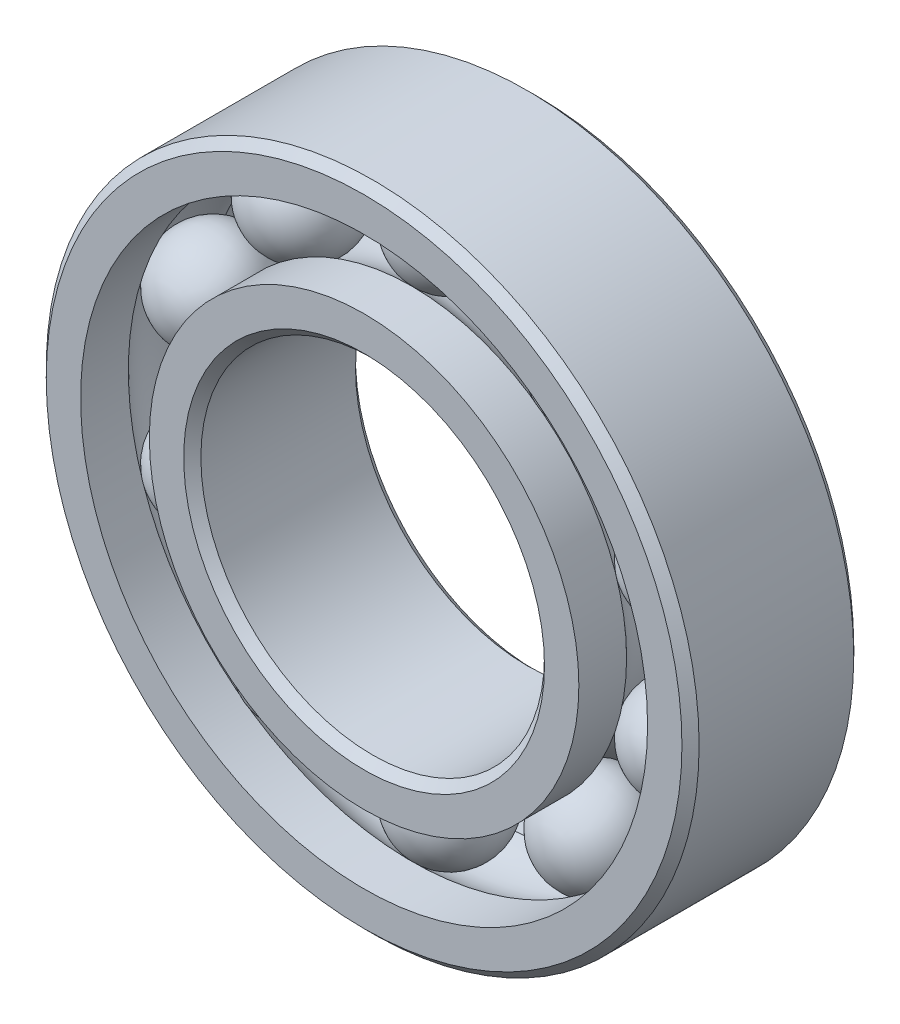
SolidWorks part; units mm, degrees
ref_plane "Front Plane" through (0, 0, 0) normal (0, 0, 1) x (1, 0, 0)
ref_plane "Top Plane" through (0, 0, 0) normal (0, 1, 0) x (1, 0, 0)
ref_plane "Right Plane" through (0, 0, 0) normal (1, 0, 0) x (0, 0, -1)
sketch "Sketch1" plane through (0, 0, 0) normal (0, 0, 1) x (1, 0, 0)
  circle A0 centre (0, 0) radius 9.5
  circle A1 centre (0, 0) radius 5
  dimension "OD" = 19
  dimension "ID" = 10
  dimension "For Shaft Diameter" = 10
  dimension "For Housing ID" = 19
sketch "Sketch5" plane through (0, 0, 0) normal (1, 0, 0) x (0, 0, -1)
  line L0 (-2.5, 0) -> (2.5, 0) construction
  line L1 (0, 9.5) -> (0, -9.5) construction
  line L2 (2.25, 9.5) -> (-2.25, 9.5)
  line L3 (-2.25, 9.5) -> (-2.5, 9.25)
  line L4 (-2.5, 9.25) -> (-2.5, 8.25)
  line L5 (-2.5, 8.25) -> (-1.1111, 8.25)
  line L6 (2.5, 8.25) -> (1.1111, 8.25)
  line L7 (2.5, 9.25) -> (2.5, 8.25)
  line L8 (2.25, 9.5) -> (2.5, 9.25)
  line L9 (0, 9.5) -> (0, 7.25) construction
  line L10 (0, 7.25) -> (0, 5) construction
  line L11 (-1.4948, 7.25) -> (-2.5, 7.25) construction
  line L12 (1.8069, 6.2754) -> (2.1879, 6.2754) construction
  line L13 (-1.8069, 6.2754) -> (-2.1879, 6.2754) construction
  line L14 (-1.8069, 6.2754) -> (-1.8069, 8.2246) construction
  line L15 (-1.8069, 8.2246) -> (-2.1879, 8.2246) construction
  line L16 (-2.1879, 6.2754) -> (-2.1879, 8.2246) construction
  line L17 (-1.8069, 6.2754) -> (-2.1879, 8.2246) construction
  line L18 (-1.8069, 8.2246) -> (-2.1879, 6.2754) construction
  line L19 (2.1879, 6.2754) -> (2.1879, 8.2246) construction
  line L20 (1.8069, 8.2246) -> (2.1879, 8.2246) construction
  line L21 (1.8069, 6.2754) -> (1.8069, 8.2246) construction
  line L22 (0, 9.5) -> (0, -9.5) construction
  arc A0 (-1.1111, 8.25) -> (1.1111, 8.25) centre (0, 7.25) cw
  circle A1 centre (0, 7.25) radius 1.4948 construction
  point P14 (0, 5)
  point P15 (-1.9974, 7.25)
  dimension "Width" = 5
  dimension "D1" = 45
  dimension "D2" = 0.25
  dimension "D3" = 2.2222
  dimension "D4" = 1
  dimension "D5" = 0.381
  dimension "D6" = 0.0254
  dimension "D7" = 5
revolve "Revolve1" add sketch "Sketch5" angle 360 about L0
sketch "Sketch3" plane through (0, 0, 0) normal (1, 0, 0) x (0, 0, -1)
  line L0 (-2.5, 6.25) -> (-1.1111, 6.25)
  line L1 (0, 9.5) -> (0, -9.5) construction
  line L2 (-2.5, 9.25) -> (-2.5, 8.25) construction
  line L3 (-2.5, 6.25) -> (-2.5, 5.25)
  line L4 (-2.25, 9.5) -> (-2.5, 9.25) construction
  line L5 (-2.5, 5.25) -> (-2.25, 5)
  line L6 (-2.25, 5) -> (2.25, 5)
  line L7 (2.25, 9.5) -> (2.25, -9.5) construction
  line L8 (2.25, 5) -> (2.5, 5.25)
  line L9 (2.5, -9.25) -> (2.5, 9.25) construction
  line L10 (2.5, 5.25) -> (2.5, 6.25)
  line L11 (2.5, 6.25) -> (1.1111, 6.25)
  line L13 (2.25, 9.5) -> (2.5, 9.25) construction
  arc A0 (1.1111, 8.25) -> (-1.1111, 8.25) centre (0, 7.25) ccw construction
  arc A1 (1.1111, 6.25) -> (-1.1111, 6.25) centre (0, 7.25) cw
revolve "Revolve3" add sketch "Sketch3" angle 360 about L0
sketch "Sketch4" plane through (0, 0, 0) normal (1, 0, 0) x (0, 0, -1)
  line L0 (-1.4948, 7.25) -> (1.4948, 7.25)
  arc A2 (-1.4948, 7.25) -> (1.4948, 7.25) centre (0, 7.25) cw
  arc A3 (1.1111, 8.25) -> (-1.1111, 8.25) centre (0, 7.25) ccw construction
revolve "Revolve4" add sketch "Sketch4" angle 360 about L0
pattern_circular "CirPattern1" count 10 every 36 of bodies 104
ref_axis "Center Axis 1" through (0, 0, -2.25) along (0, 0, 1)
equation "\"D2@Sketch5\" = \"Width@Sketch5\" * .05"
equation "\"D3@Sketch5\" = \"Width@Sketch5\" / 2.25"
equation "\"D4@Sketch5\"=((\"OD@Sketch1\"-\"ID@Sketch1\")/2)/4.5"
equation "\"D2@CirPattern1\" = 360/\"Balls@CirPattern1\""
